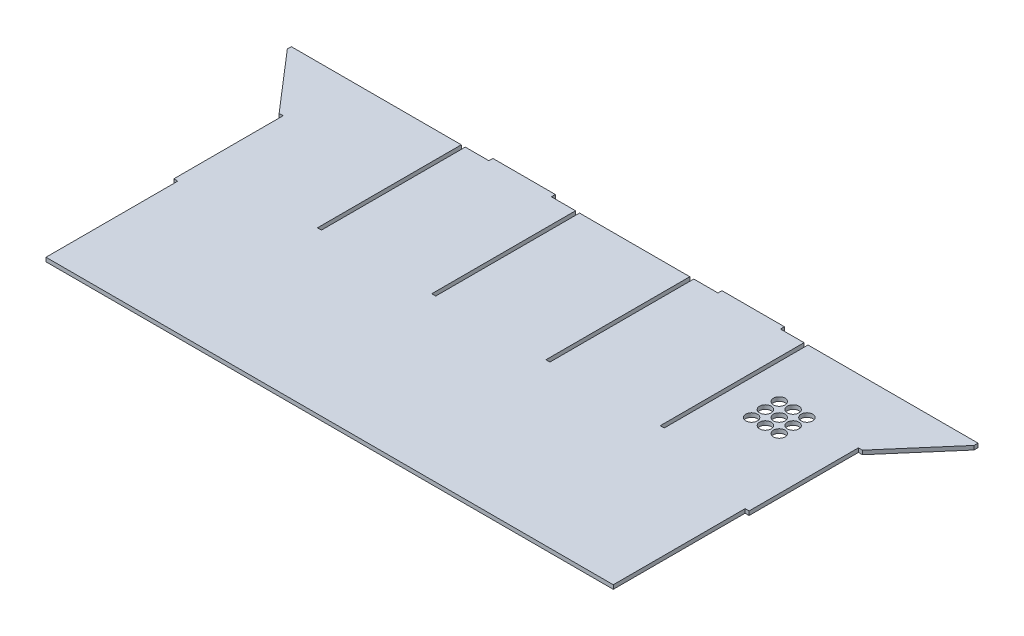
SolidWorks part; units mm, degrees
material "6061-T6 (SS)"
ref_plane "X-Y Datum" through (0, 0, 0) normal (0, 0, 1) x (1, 0, 0)
ref_plane "X-Z Datum" through (0, 0, 0) normal (0, 1, 0) x (1, 0, 0)
ref_plane "Y-Z Datum" through (0, 0, 0) normal (1, 0, 0) x (0, 0, -1)
sketch "Sketch1" plane through (0, 0, 0) normal (0, 0, 1) x (1, 0, 0)
  line L1 (-228.601, -1.5875) -> (228.601, -1.5875)
  line L2 (-228.601, -1.5875) -> (-228.601, 1.5875)
  line L3 (-228.601, 1.5875) -> (228.601, 1.5875)
  line L4 (228.601, -1.5875) -> (228.601, 1.5875)
  line L5 (-228.601, -1.5875) -> (228.601, 1.5875) construction
  line L6 (-228.601, 1.5875) -> (228.601, -1.5875) construction
  point P0 (0, 0)
  dimension "D1" = 3.175
  dimension "D2" = 457.202
extrude "Boss-Extrude1" add sketch "Sketch1" along normal blind 242.425
sketch "Sketch2" plane through (0, 1.5875, 0) normal (0, 1, 0) x (1, 0, 0)
  line L0 (228.601, 0) -> (225.426, 0)
  line L1 (228.601, 0) -> (-228.601, 0) construction
  line L2 (225.426, 0) -> (137.796, 0)
  line L3 (137.796, 0) -> (134.621, 0)
  line L10 (134.621, 0) -> (137.796, 0)
  line L11 (134.621, 0) -> (134.621, -114.3)
  line L12 (134.621, -114.3) -> (137.796, -114.3)
  line L13 (137.796, 0) -> (137.796, -114.3)
  line M2 (228.601, 0) -> (-228.601, 0)
  dimension "D1" = 87.63
  dimension "D2" = 3.175
  dimension "D3" = 114.3
  dimension "D4" = 3.175
extrude "Cut-Extrude1" cut sketch "Sketch2" against normal through all contours L13 L11 L12 M2 region at (136.2085, 1.5875, 57.15)
pattern_linear "LPattern1" count 4 spacing 90.807 along (-1, 0, 0) of "Cut-Extrude1"
sketch "Sketch3" plane through (0, 0, 0) normal (0, 0, -1) x (-1, 0, 0)
  line L1 (-115.8495, 1.5875) -> (-66.1907, 1.5875)
  line L2 (-115.8495, 1.5875) -> (-115.8495, -1.5875)
  line L3 (-115.8495, -1.5875) -> (-66.1907, -1.5875)
  line L4 (-66.1907, 1.5875) -> (-66.1907, -1.5875)
  line L5 (66.1907, 1.5875) -> (115.8495, 1.5875)
  line L6 (66.1907, 1.5875) -> (66.1907, -1.5875)
  line L7 (66.1907, -1.5875) -> (115.8495, -1.5875)
  line L8 (115.8495, 1.5875) -> (115.8495, -1.5875)
extrude "Boss-Extrude2" add sketch "Sketch3" along normal blind 3.175
sketch "Sketch4" plane through (0, -1.5875, 0) normal (0, -1, 0) x (1, 0, 0)
  line L0 (-228.601, 0) -> (-272.876, 0)
  line L2 (-228.601, 242.425) -> (-228.601, 0) construction
  line L3 (-228.601, 50.8) -> (-228.601, 0)
  line L4 (-272.876, 0) -> (-272.876, 3.175)
  line L6 (-228.601, 50.8) -> (-231.776, 50.8)
  line L7 (-231.776, 50.8) -> (-272.876, 3.175)
  dimension "D1" = 44.275
  dimension "D2" = 50.8
  dimension "D3" = 3.175
  dimension "D4" = 3.175
extrude "Boss-Extrude3" add sketch "Sketch4" against normal blind 3.175
mirror "Mirror1" about plane through (0, 0, 0) normal (1, 0, 0) of "Boss-Extrude3"
sketch "Sketch5" plane through (0, -1.5875, 0) normal (0, -1, 0) x (1, 0, 0)
  line L1 (-228.601, 242.425) -> (-225.426, 242.425)
  line L2 (-228.601, 242.425) -> (-228.601, 137.65)
  line L3 (-228.601, 137.65) -> (-225.426, 137.65)
  line L4 (-225.426, 242.425) -> (-225.426, 137.65)
  dimension "D1" = 3.175
  dimension "D2" = 104.775
extrude "Cut-Extrude2" cut sketch "Sketch5" against normal blind 3.175
mirror "Mirror2" about plane through (0, 0, 0) normal (1, 0, 0) of "Cut-Extrude2"
sketch "Sketch24" plane through (0, 1.5875, 0) normal (0, 1, 0) x (1, 0, 0)
  circle A2 centre (168.1884, -46.0366) radius 0.0637
  circle A5 centre (165.2818, -50.3636) radius 4.648
extrude "Cut-Extrude7" cut sketch "Sketch24" against normal through all
pattern_linear "LPattern17" count 3 spacing 11 along (1, 0, 0) of "Cut-Extrude7"
pattern_linear "LPattern18" count 3 spacing 11 along (0, 0, 1) of "LPattern17"
